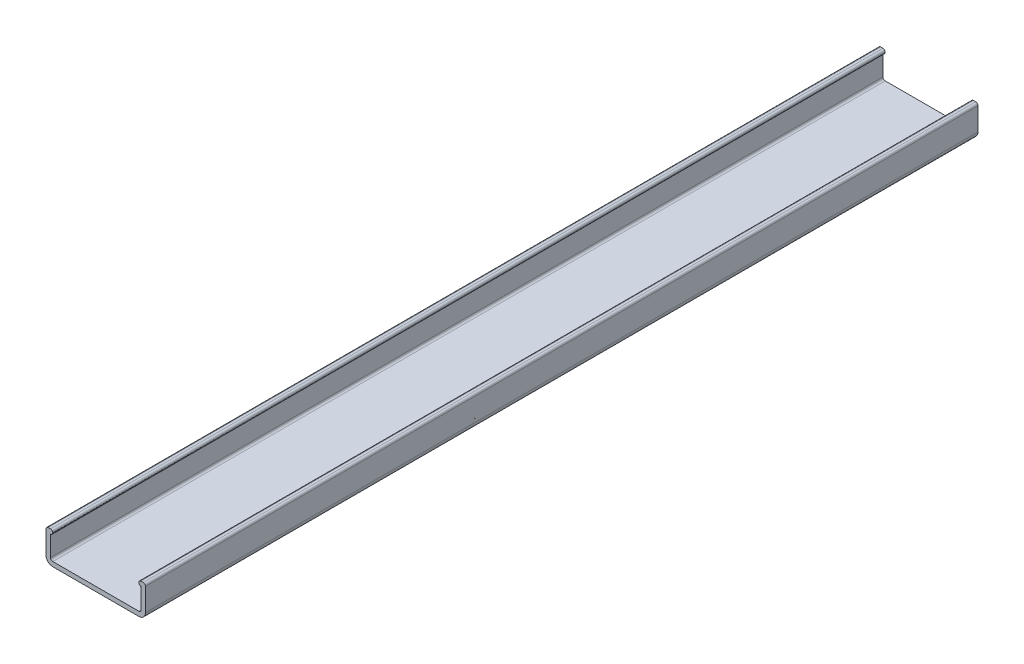
SolidWorks part; units mm, degrees
ref_plane "Front Plane" through (0, 0, 0) normal (0, 0, 1) x (1, 0, 0)
ref_plane "Top Plane" through (0, 0, 0) normal (0, 1, 0) x (1, 0, 0)
ref_plane "Right Plane" through (0, 0, 0) normal (1, 0, 0) x (0, 0, -1)
sketch "Sketch1" plane through (0, 0, 0) normal (0, 0, 1) x (1, 0, 0)
  line L0 (-17.4625, 11.1125) -> (-17.4625, 0)
  line L1 (-17.4625, 0) -> (17.4625, 0)
  line L2 (17.4625, 0) -> (17.4625, 11.1125)
  line L4 (-15.875, 1.5875) -> (15.875, 1.5875)
  line L8 (15.875, 1.5875) -> (15.875, 9.525)
  line L9 (15.875, 1.5875) -> (15.875, 11.1125) construction
  line L10 (-15.875, 11.1125) -> (-15.875, 1.5875) construction
  line L11 (15.875, 9.525) -> (15.0813, 9.525)
  line L12 (15.0813, 9.525) -> (15.0813, 11.1125)
  line L13 (15.0813, 11.1125) -> (17.4625, 11.1125)
  line L14 (-17.4625, 11.1125) -> (-15.0813, 11.1125)
  line L15 (-15.0813, 11.1125) -> (-15.0813, 9.525)
  line L16 (-15.0813, 9.525) -> (-15.875, 9.525)
  line L17 (-15.875, 9.525) -> (-15.875, 1.5875)
  line L18 (0, 0) -> (0, 11.7405) construction
  dimension "D1" = 34.925
  dimension "D2" = 11.1125
  dimension "D4" = 1.5875
  dimension "D5" = 0.7937
  dimension "D3" = 1.5875
extrude "Boss-Extrude1" add sketch "Sketch1" along normal blind 292.1
fillet "Fillet1" radius 0.7937 8 edges at (15.875, 1.5875, 146.05) (-15.875, 1.5875, 146.05) (-15.0813, 9.525, 146.05) (-15.0813, 11.1125, 146.05) (-17.4625, 11.1125, 146.05) (17.4625, 11.1125, 146.05) (15.0813, 11.1125, 146.05) (15.0813, 9.525, 146.05)
fillet "Fillet2" radius 2.3495 2 edges at (17.4625, 0, 146.05) (-17.4625, 0, 146.05)
